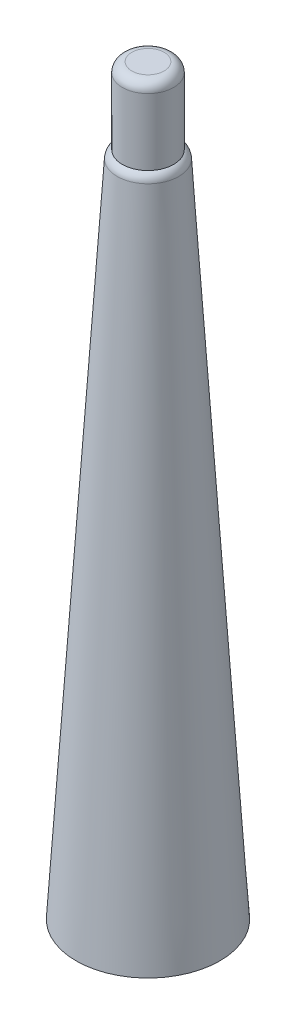
SolidWorks part; units mm, degrees
ref_plane "Front Plane" through (0, 0, 0) normal (0, 0, 1) x (1, 0, 0)
ref_plane "Top Plane" through (0, 0, 0) normal (0, 1, 0) x (1, 0, 0)
ref_plane "Right Plane" through (0, 0, 0) normal (1, 0, 0) x (0, 0, -1)
sketch "Sketch2" plane through (0, 0, 0) normal (0, 0, 1) x (1, 0, 0)
  line L0 (0, 0) -> (-19.177, 0)
  line L1 (-19.177, 0) -> (-8.0842, 177.8)
  line L2 (-8.0842, 177.8) -> (0, 177.8)
  line L3 (0, 177.8) -> (0, 0)
  dimension "D1" = 19.177
  dimension "D2" = 177.8
  dimension "D3" = 3.57
revolve "Revolve1" add sketch "Sketch2" angle 360 about L3
sketch "Sketch3" plane through (0, 0, 0) normal (0, -1, 0) x (1, 0, 0)
  circle A0 centre (0, 0) radius 3.5814
  dimension "D1" = 7.1628
extrude "Cut-Extrude1" cut sketch "Sketch3" against normal blind 5.08
shell "Shell1" thickness 2.54
sketch "Sketch4" plane through (0, 177.8, 0) normal (0, 1, 0) x (1, 0, 0)
  circle A0 centre (0, 0) radius 6.8508
extrude "Boss-Extrude1" add sketch "Sketch4" along normal blind 20.32
fillet "Fillet1" radius 2.54 2 edges at (-8.0842, 177.8, 0) (-6.8508, 198.12, 0)
